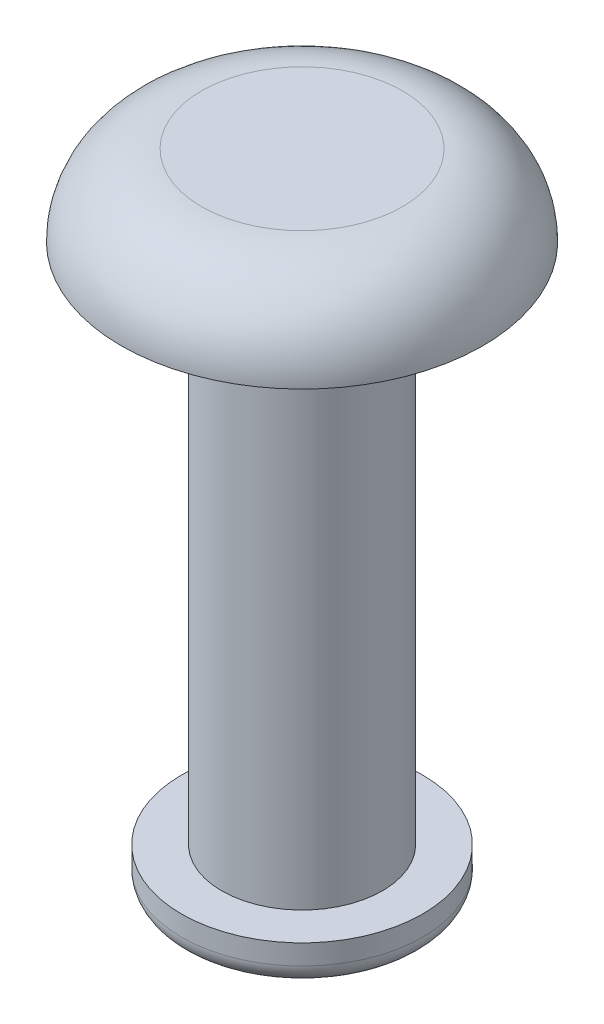
SolidWorks part; units mm, degrees
material "Hierro dúctil"
ref_plane "Alzado" through (0, 0, 0) normal (0, 0, 1) x (1, 0, 0)
ref_plane "Planta" through (0, 0, 0) normal (0, 1, 0) x (1, 0, 0)
ref_plane "Vista lateral" through (0, 0, 0) normal (1, 0, 0) x (0, 0, -1)
sketch "Croquis1" plane through (0, 0, 0) normal (0, 1, 0) x (1, 0, 0)
  circle A0 centre (0, 0) radius 4.5
  dimension "D1" = 9
extrude "Saliente-Extruir1" add sketch "Croquis1" along normal blind 2
sketch "Croquis2" plane through (0, 0, 0) normal (0, -1, 0) x (1, 0, 0)
  circle A0 centre (0, 0) radius 2
  dimension "D1" = 4
extrude "Saliente-Extruir2" add sketch "Croquis2" along normal blind 13
fillet "Redondeo1" radius 2 1 edges at (0, 2, 4.5)
sketch "Croquis3" plane through (0, -13, 0) normal (0, -1, 0) x (-1, 0, 0)
  circle A0 centre (0, 0) radius 3
  dimension "D1" = 6
extrude "Saliente-Extruir3" add sketch "Croquis3" along normal blind 1
fillet "Redondeo2" radius 0.5 1 edges at (0, -14, -3)
